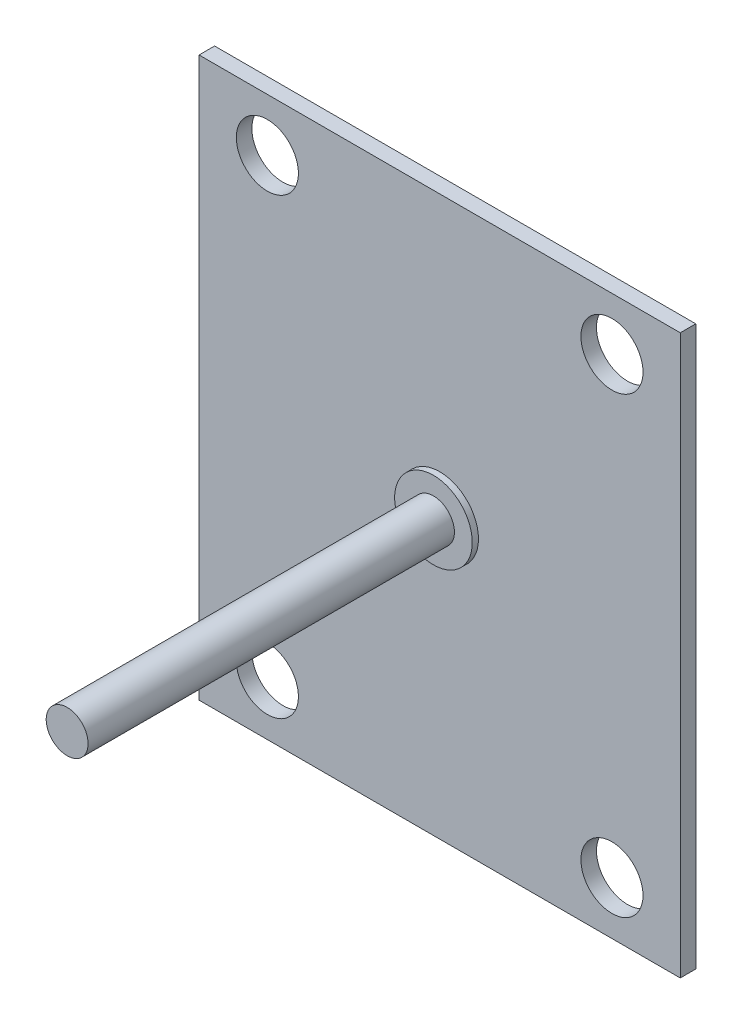
SolidWorks part; units mm, degrees
ref_plane "Front Plane" through (0, 0, 0) normal (0, 0, 1) x (1, 0, 0)
ref_plane "Top Plane" through (0, 0, 0) normal (0, 1, 0) x (1, 0, 0)
ref_plane "Right Plane" through (0, 0, 0) normal (1, 0, 0) x (0, 0, -1)
sketch "Sketch1" plane through (0, 0, 0) normal (0, 0, 1) x (1, 0, 0)
  line L0 (0, 117.9674) -> (0, -118.3343) construction
  line L1 (77.5, -90) -> (-77.5, -90)
  line L2 (77.5, -90) -> (77.5, 90)
  line L3 (77.5, 90) -> (-77.5, 90)
  line L4 (-77.5, -90) -> (-77.5, 90)
  line L5 (77.5, -90) -> (-77.5, 90) construction
  line L6 (77.5, 90) -> (-77.5, -90) construction
  line L7 (-138.8823, 0) -> (134.846, 0) construction
  circle A0 centre (0, 0) radius 5.75
  circle A1 centre (0, 0) radius 6.75
  circle A2 centre (0, 0) radius 12.5
  circle A3 centre (-55.5, -73) radius 10
  circle A4 centre (55.5, -73) radius 10
  circle A5 centre (55.5, 73) radius 10
  circle A6 centre (-55.5, 73) radius 10
  dimension "D1" = 11.5
  dimension "D2" = 13.5
  dimension "D3" = 25
  dimension "D8" = 20
  dimension "D4" = 155
  dimension "D5" = 180
extrude "Boss-Extrude1" add sketch "Sketch1" along normal blind 5 contours L4 L1 L2 L3 A4 A3 A2 A5 A6 region at (0, -87.6246, 0)
extrude "Boss-Extrude2" add sketch "Sketch1<3>" along normal blind 7 contours A2 A1 region at (-12.1464, 0, 0)
sketch "Sketch1<3>" plane through (0, 0, 0) normal (0, 0, 1) x (1, 0, 0) same geometry as "Sketch1"
extrude "Boss-Extrude3" add sketch "Sketch1<4>" along normal blind 125 contours A1 A0 | A0 region at (0, 0, 0) region at (-6.5591, 0, 0)
sketch "Sketch1<4>" plane through (0, 0, 0) normal (0, 0, 1) x (1, 0, 0) same geometry as "Sketch1"
extrude "Cut-Extrude1" cut sketch "Sketch1<5>" along normal blind 120 contours A0 region at (0, 0, 0)
sketch "Sketch1<5>" plane through (0, 0, 0) normal (0, 0, 1) x (1, 0, 0) same geometry as "Sketch1"
ref_plane "Plane1" through (0, 0, 15) normal (0, 0, 1) x (1, 0, 0)
sketch "Sketch2" plane through (0, 0, 15) normal (0, 0, 1) x (1, 0, 0)
  line L1 (3, -8.2612) -> (-3, -8.2612)
  line L2 (3, -8.2612) -> (3, -5.2388)
  line L3 (3, -5.2388) -> (-3, -5.2388)
  line L4 (-3, -8.2612) -> (-3, -5.2388)
  line L5 (3, -8.2612) -> (-3, -5.2388) construction
  line L6 (3, -5.2388) -> (-3, -8.2612) construction
  circle A0 centre (0, 0) radius 6.75 construction
  circle A1 centre (0, 0) radius 6.75 construction
  point P0 (0, -6.75)
  dimension "D1" = 6
extrude "Cut-Extrude2" cut sketch "Sketch2" along normal blind 80
